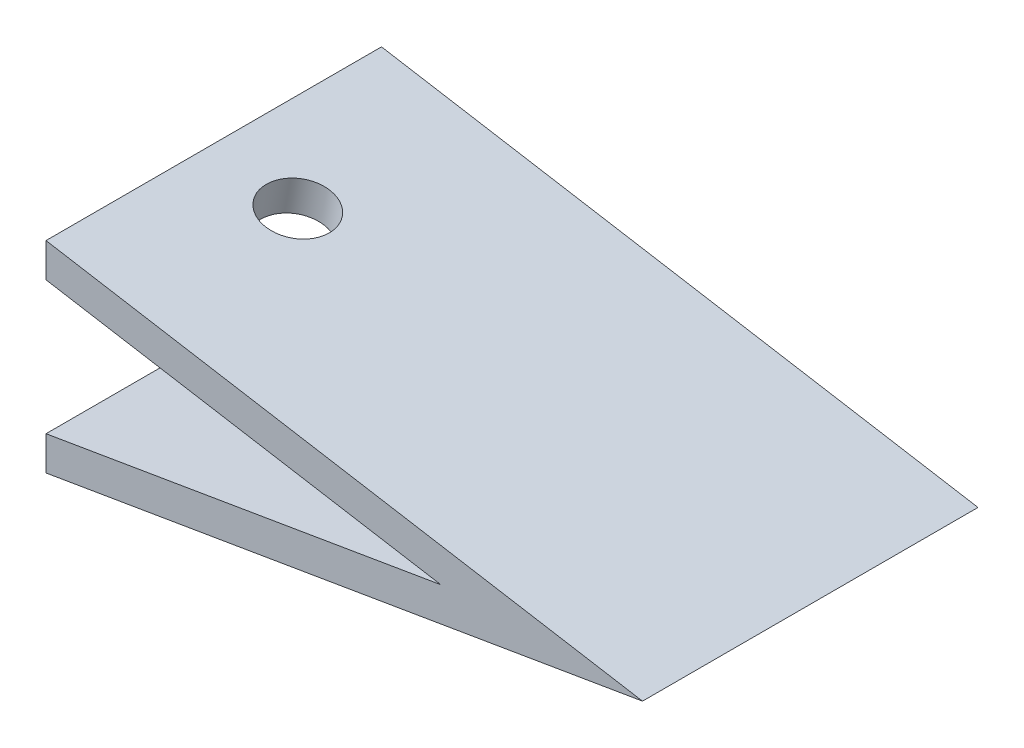
SolidWorks part; units mm, degrees
ref_plane "Front Plane" through (0, 0, 0) normal (0, 0, 1) x (1, 0, 0)
ref_plane "Top Plane" through (0, 0, 0) normal (0, 1, 0) x (1, 0, 0)
ref_plane "Right Plane" through (0, 0, 0) normal (1, 0, 0) x (0, 0, -1)
sketch "Sketch1" plane through (0, 0, 0) normal (0, 0, 1) x (1, 0, 0)
  line L0 (0, 0) -> (88.9, 0) construction
  line L1 (88.9, 0) -> (0, 15)
  line L2 (88.9, 0) -> (0, -15)
  line L3 (0, 15) -> (0, 0)
  line L4 (0, -15) -> (0, 0)
  line L5 (58.8478, 0) -> (0, 9.9293)
  line L6 (58.8478, 0) -> (0, -9.9293)
  dimension "D1" = 15
  dimension "D2" = 5
  dimension "D3" = 88.9
extrude "Extrude1" add sketch "Sketch1" along normal blind 5 contours L5 L0 L1 L3 | L3 L0 L5 | L0 L4 L6 | L0 L6 L4 L2 region at (19.6159, 3.3098, 0) region at (19.6159, -3.3098, 0) region at (37.4463, 6.3183, 0) region at (37.4463, -6.3183, 0)
extrude "Extrude2" add sketch "Sketch1<4>" along normal blind 50 contours L5 L0 L1 L3 | L0 L6 L4 L2 region at (37.4463, 6.3183, 0) region at (37.4463, -6.3183, 0)
sketch "Sketch1<4>" plane through (0, 0, 0) normal (0, 0, 1) x (1, 0, 0) same geometry as "Sketch1"
sketch "Sketch3" plane through (0, 0, 5) normal (0, 0, 1) x (1, 0, 0)
  circle A0 centre (12.7, 0) radius 4.7625
  dimension "D1" = 9.525
  dimension "D2" = 12.7
extrude "Extrude3" cut sketch "Sketch3" against normal through all
sketch "Sketch4" plane through (2.4609, -14.5848, 0) normal (0.1664, -0.9861, 0) x (0.9861, 0.1664, 0)
  line L0 (-2.4957, 25) -> (87.6609, 25) construction
  line L1 (-2.4957, 50) -> (-2.4957, 0) construction
  line L2 (87.6609, 50) -> (87.6609, 0) construction
  circle A0 centre (10.2043, 25) radius 4.7625
  dimension "D1" = 9.525
  dimension "D2" = 12.7
extrude "Extrude4" cut sketch "Sketch4" against normal up to next
sketch "Sketch5" plane through (2.4609, 14.5848, 0) normal (0.1664, 0.9861, 0) x (0.9861, -0.1664, 0)
  line L0 (87.6609, -25) -> (-2.4957, -25) construction
  line L1 (87.6609, -50) -> (87.6609, 0) construction
  line L2 (-2.4957, -50) -> (-2.4957, 0) construction
  circle A0 centre (10.2043, -25) radius 4.7625
  dimension "D2" = 9.525
  dimension "D1" = 12.7
extrude "Extrude5" cut sketch "Sketch5" against normal up to next
